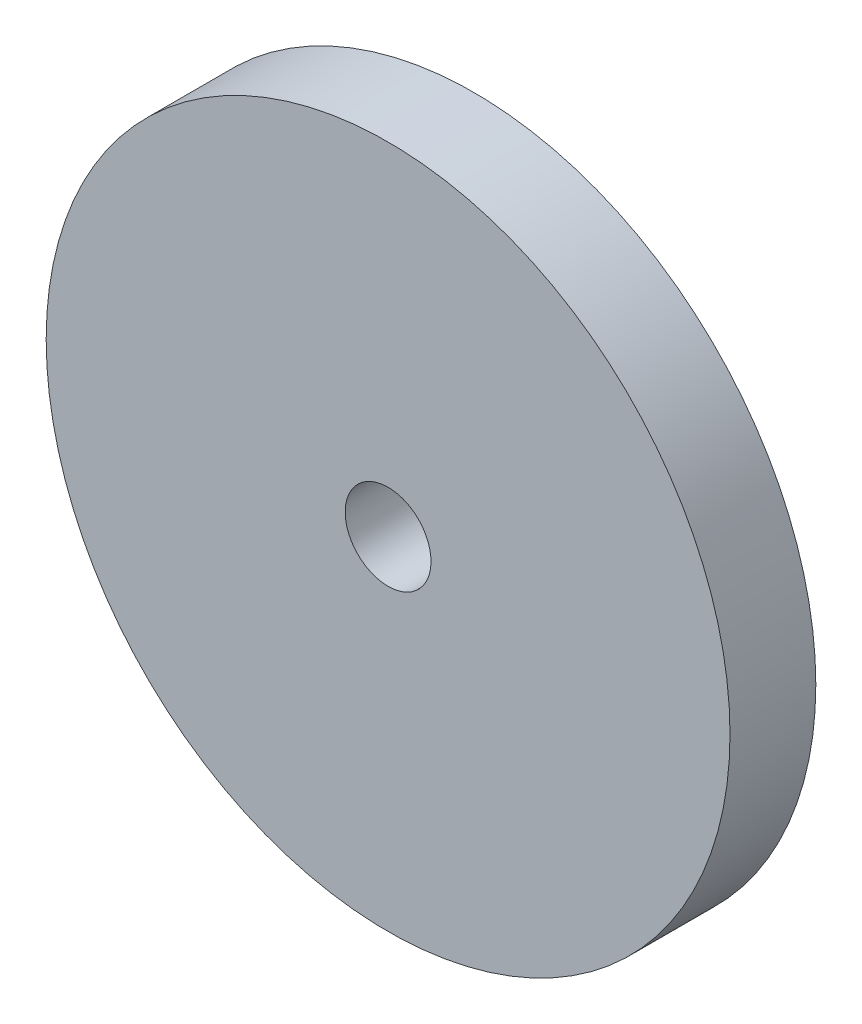
SolidWorks part; units mm, degrees
ref_plane "Front Plane" through (0, 0, 0) normal (0, 0, 1) x (1, 0, 0)
ref_plane "Top Plane" through (0, 0, 0) normal (0, 1, 0) x (1, 0, 0)
ref_plane "Right Plane" through (0, 0, 0) normal (1, 0, 0) x (0, 0, -1)
sketch "Sketch1" plane through (0, 0, 0) normal (0, 0, 1) x (1, 0, 0)
  circle A0 centre (0, 0) radius 202.4
  circle A1 centre (0, 0) radius 25.4
  dimension "D1" = 404.8
  dimension "D2" = 50.8
extrude "Boss-Extrude1" add sketch "Sketch1" along normal blind 50.8 contours A0 | A1
